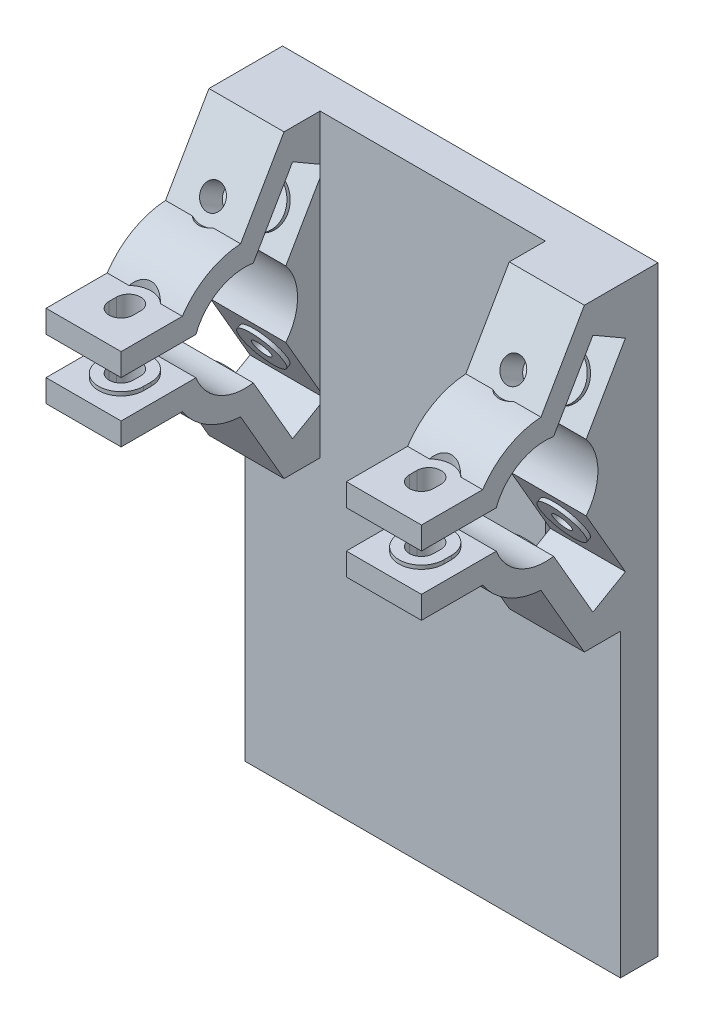
SolidWorks part; units mm, degrees
ref_plane "Спереди" through (0, 0, 0) normal (0, 0, 1) x (1, 0, 0)
ref_plane "Сверху" through (0, 0, 0) normal (0, 1, 0) x (1, 0, 0)
ref_plane "Справа" through (0, 0, 0) normal (1, 0, 0) x (0, 0, -1)
sketch "Эскиз1" plane through (0, 0, 0) normal (1, 0, 0) x (0, 0, -1)
  line L0 (0, 40) -> (0, -40)
  line L1 (0, -40) -> (5, -40)
  line L2 (5, -40) -> (5, 40)
  line L3 (5, 40) -> (0, 40)
  line L4 (-54.4681, 0) -> (-52.8723, 0) construction
  line L5 (-53.8298, 20) -> (-1.5957, 20) construction
  line L6 (-10, 20) -> (-4.0021, 30.3886) construction
  line L7 (-10, 20) -> (-4.0021, 9.6114) construction
  line L8 (-8.8959, 26.9124) -> (-3.6651, 35.9724)
  line L9 (-3.6651, 35.9724) -> (0.6651, 33.4724)
  line L10 (0.6651, 33.4724) -> (-4.5658, 24.4124)
  line L11 (-4.5658, 15.5876) -> (0.6651, 6.5276)
  line L12 (0.6651, 6.5276) -> (-3.6651, 4.0276)
  line L13 (-3.6651, 4.0276) -> (-8.8959, 13.0876)
  line L14 (-7.5263, 14.5) -> (-6.4737, 15.1077) construction
  line L15 (-7.5263, 25.5) -> (-6.4737, 24.8923) construction
  line L16 (-16.5383, 17.5) -> (-26.5, 17.5)
  line L17 (-26.5, 17.5) -> (-26.5, 14.5)
  line L18 (-26.5, 14.5) -> (-18.3516, 14.5)
  line L19 (-10.5873, 10.0173) -> (-4.8038, 0)
  line L20 (-4.8038, 0) -> (0, 0)
  line L21 (-16.5383, 22.5) -> (-26.5, 22.5)
  line L22 (-26.5, 22.5) -> (-26.5, 25.5)
  line L23 (-26.5, 25.5) -> (-18.3516, 25.5)
  line L24 (-10.5873, 29.9827) -> (-4.8038, 40)
  line L25 (-16, 18.4961) -> (-16, 21.5039) construction
  line L26 (-4.8038, 40) -> (0, 40)
  arc A0 (-4.5658, 15.5876) -> (-4.5658, 24.4124) centre (-10, 20) ccw
  arc A1 (-8.8959, 26.9124) -> (-16.5383, 22.5) centre (-10, 20) ccw
  arc A2 (-8.8959, 13.0876) -> (-16.5383, 17.5) centre (-10, 20) cw
  circle A3 centre (-10, 20) radius 6 construction
  arc A4 (-18.3516, 14.5) -> (-10.5873, 10.0173) centre (-10, 20) ccw
  arc A5 (-18.3516, 25.5) -> (-10.5873, 29.9827) centre (-10, 20) cw
  point P4 (0, 0)
  point P28 (-1.5, 34.7224)
  point P29 (-7, 25.1962)
  point P30 (-1.5, 5.2776)
  point P31 (-1.5, 5.2776)
  point P32 (-7, 14.8038)
  point P47 (-16, 20)
  dimension "D4" = 7
  dimension "D6" = 12
  dimension "D16" = 3
  dimension "D1" = 5
  dimension "D2" = 80
  dimension "D3" = 20
  dimension "D5" = 10
  dimension "D7" = 120
  dimension "D8" = 60
  dimension "D9" = 5
  dimension "D10" = 5
  dimension "D11" = 11
  dimension "D12" = 11
  dimension "D13" = 10.5
  dimension "D14" = 5
  dimension "D15" = 3
  dimension "D17" = 3
  dimension "D18" = 3
extrude "Бобышка-Вытянуть1" add sketch "Эскиз1" along normal blind 50 contours L0 L1 L2 L3
extrude "Бобышка-Вытянуть2" add sketch "Эскиз1<3>" along normal blind 10 contours L18 A4 L19 L20 L0 L12 L13 A2 L16 L17 | A0 L11 L0 L10 | A5 L23 L22 L21 A1 L8 L9 L0 L26 L24 region at (0, 0.3176, 2.4019) region at (0, 20, 1.6399) region at (0, 36.9282, 0.3176)
sketch "Эскиз1<3>" plane through (0, 0, 0) normal (1, 0, 0) x (0, 0, -1) same geometry as "Эскиз1"
ref_axis "Ось1" through (10, 20, 10) along (-1, 0, 0)
sketch "Эскиз6" plane through (0, 8.0801, 13.9952) normal (0, 0.5, 0.866) x (1, 0, 0)
  line L0 (0, 25.5074) -> (10, 25.5074)
  line L1 (0, 27.9904) -> (0, 18.8589) construction
  line L2 (10, 27.9904) -> (10, 18.8589) construction
  line L3 (10, 25.5074) -> (10, 29.3205)
  line L4 (10, 29.3205) -> (0, 29.3205)
  line L5 (0, 29.3205) -> (0, 25.5074)
  line L6 (10, 12.3205) -> (0, 12.3205) construction
  dimension "D1" = 17
extrude "Вырез-Вытянуть10" cut sketch "Эскиз6" along normal blind 1
sketch "Эскиз2" plane through (0, 8.0801, 13.9952) normal (0, 0.5, 0.866) x (1, 0, 0)
  line L0 (10, 12.3205) -> (0, 12.3205) construction
  line L1 (5, -6.6465) -> (5, 40.453) construction
  line L2 (10, -2.4019) -> (0, -2.4019) construction
  circle A0 centre (5, 23.3205) radius 1.25
  circle A1 centre (5, 23.3205) radius 1.6
  circle A2 centre (5, 23.3205) radius 3
  point P6 (5, -2.4019)
  dimension "D2" = 2.5
  dimension "D3" = 3.2
  dimension "D4" = 6
  dimension "D1" = 11
extrude "Бобышка-Вытянуть3" add sketch "Эскиз2" along normal blind 0.5 contours A2
extrude "Бобышка-Вытянуть4" add sketch "Эскиз2<3>" against normal blind 0.5 from offset 5 contours A2
sketch "Эскиз2<3>" plane through (0, 8.0801, 13.9952) normal (0, 0.5, 0.866) x (1, 0, 0) same geometry as "Эскиз2"
extrude "Вырез-Вытянуть1" cut sketch "Эскиз2<4>" against normal blind 10 from offset 0.5 contours A0
sketch "Эскиз2<4>" plane through (0, 8.0801, 13.9952) normal (0, 0.5, 0.866) x (1, 0, 0) same geometry as "Эскиз2"
extrude "Вырез-Вытянуть4" cut sketch "Эскиз2<5>" along normal blind 1 from offset 8 contours A2
sketch "Эскиз2<5>" plane through (0, 8.0801, 13.9952) normal (0, 0.5, 0.866) x (1, 0, 0) same geometry as "Эскиз2"
extrude "Вырез-Вытянуть5" cut sketch "Эскиз2<6>" along normal blind 3.5 from offset 4.5 contours A1
sketch "Эскиз2<6>" plane through (0, 8.0801, 13.9952) normal (0, 0.5, 0.866) x (1, 0, 0) same geometry as "Эскиз2"
ref_plane "Плоскость2" through (0, 20, 0) normal (0, -1, 0) x (-1, 0, 0)
mirror "Зеркальное отражение3" about plane through (0, 20, 0) normal (0, -1, 0) of "Вырез-Вытянуть10", "Бобышка-Вытянуть3", "Бобышка-Вытянуть4", "Вырез-Вытянуть1", "Вырез-Вытянуть4", "Вырез-Вытянуть5"
sketch "Эскиз3" plane through (0, 25.5, 0) normal (0, 1, 0) x (1, 0, 0)
  line L0 (10, -26.5) -> (0, -26.5) construction
  line L1 (5, -30.7803) -> (5, -14.9973) construction
  line L2 (5, -20.5) -> (5, -21.5) construction
  line L3 (6.6, -20.5) -> (6.6, -21.5)
  line L4 (3.4, -20.5) -> (3.4, -21.5)
  line L5 (5, -20.5) -> (5, -21.5) construction
  line L6 (8, -20.5) -> (8, -21.5)
  line L7 (2, -20.5) -> (2, -21.5)
  line L8 (10, -10) -> (0, -10) construction
  arc A0 (6.6, -20.5) -> (3.4, -20.5) centre (5, -20.5) ccw
  arc A1 (3.4, -21.5) -> (6.6, -21.5) centre (5, -21.5) ccw
  arc A2 (8, -20.5) -> (2, -20.5) centre (5, -20.5) ccw
  arc A3 (2, -21.5) -> (8, -21.5) centre (5, -21.5) ccw
  point P0 (5, -26.5)
  point P7 (5, -21)
  point P12 (5, -21)
  dimension "D2" = 1.6
  dimension "D3" = 3
  dimension "D1" = 1
  dimension "D4" = 10.5
extrude "Бобышка-Вытянуть5" add sketch "Эскиз3" against normal blind 0.5 from offset 3 contours A3 L6 A2 L7 offset against normal yes
extrude "Бобышка-Вытянуть6" add sketch "Эскиз3<3>" along normal blind 0.5 from offset 8 contours A3 L6 A2 L7 offset against normal yes
sketch "Эскиз3<3>" plane through (0, 25.5, 0) normal (0, 1, 0) x (1, 0, 0) same geometry as "Эскиз3"
extrude "Вырез-Вытянуть6" cut sketch "Эскиз3<4>" along normal blind 2
sketch "Эскиз3<4>" plane through (0, 25.5, 0) normal (0, 1, 0) x (1, 0, 0) same geometry as "Эскиз3"
extrude "Вырез-Вытянуть7" cut sketch "Эскиз3<6>" against normal blind 11 contours A1 L3 A0 L4
sketch "Эскиз3<6>" plane through (0, 25.5, 0) normal (0, 1, 0) x (1, 0, 0) same geometry as "Эскиз3"
sketch "Эскиз4" plane through (0, 14.5, 0) normal (0, -1, 0) x (1, 0, 0)
  line L1 (5, 17.2668) -> (7.8, 18.8834)
  line L2 (7.8, 18.8834) -> (7.8, 22.1166)
  line L3 (7.8, 22.1166) -> (5, 23.7332)
  line L4 (5, 23.7332) -> (2.2, 22.1166)
  line L5 (2.2, 22.1166) -> (2.2, 18.8834)
  line L6 (2.2, 18.8834) -> (5, 17.2668)
  circle A0 centre (5, 20.5) radius 2.8 construction
  dimension "D1" = 5.6
extrude "Вырез-Вытянуть8" cut sketch "Эскиз4" along normal blind 2
ref_plane "Плоскость1" through (25, 0, 0) normal (1, 0, 0) x (0, 0, -1)
mirror "Зеркальное отражение6" about plane through (25, 0, 0) normal (1, 0, 0) of "Вырез-Вытянуть8", "Вырез-Вытянуть7", "Вырез-Вытянуть6", "Бобышка-Вытянуть6", "Бобышка-Вытянуть5", "Зеркальное отражение3", "Вырез-Вытянуть5", "Вырез-Вытянуть4", "Вырез-Вытянуть1", "Бобышка-Вытянуть4", "Бобышка-Вытянуть3", "Вырез-Вытянуть10", "Бобышка-Вытянуть2"
